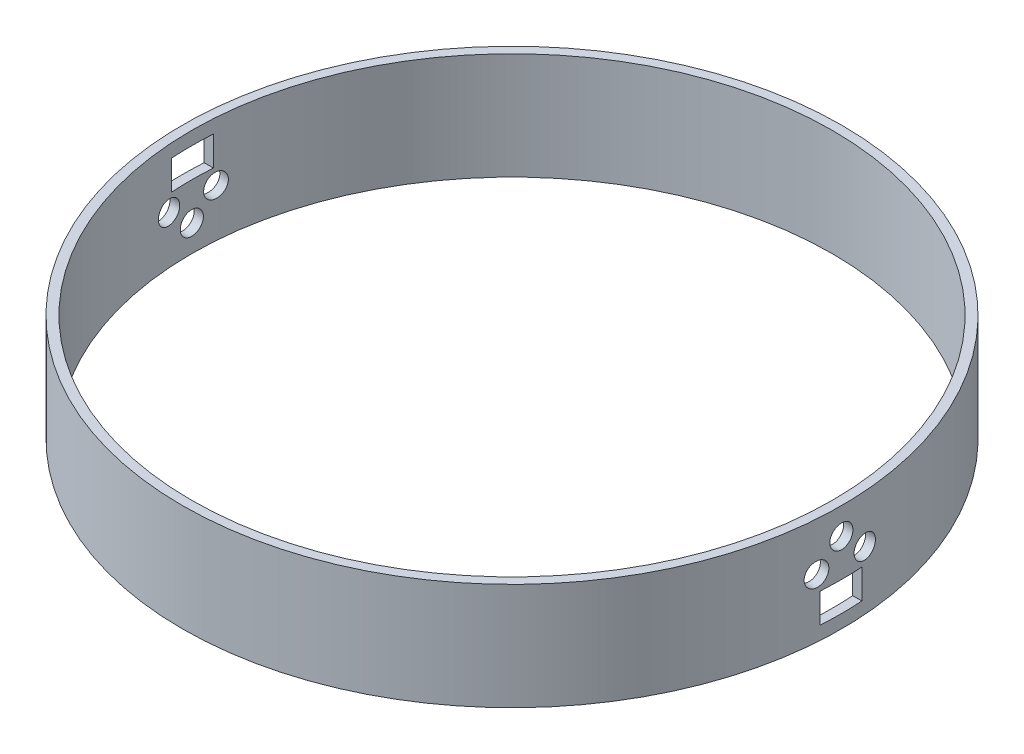
SolidWorks part; units mm, degrees
material "A-Glass Fiber"
ref_plane "Front Plane" through (0, 0, 0) normal (0, 0, 1) x (1, 0, 0)
ref_plane "Top Plane" through (0, 0, 0) normal (0, 1, 0) x (1, 0, 0)
ref_plane "Right Plane" through (0, 0, 0) normal (1, 0, 0) x (0, 0, -1)
sketch "Sketch1" plane through (0, 0, 0) normal (0, 1, 0) x (1, 0, 0)
  circle A0 centre (0, 0) radius 78.359
  circle A1 centre (0, 0) radius 76.1746
  dimension "D1" = 156.718
  dimension "D2" = 152.3492
extrude "Boss-Extrude1" add sketch "Sketch1" along normal blind 25.4
sketch "Sketch2" plane through (0, 0, 0) normal (1, 0, 0) x (0, 0, -1)
  line L0 (-78.359, 0) -> (78.359, 0) construction
  line L1 (-5, 3.175) -> (5, 3.175)
  line L2 (-5, 3.175) -> (-5, 10.175)
  line L3 (-5, 10.175) -> (5, 10.175)
  line L4 (5, 3.175) -> (5, 10.175)
  line L5 (-5, 3.175) -> (5, 10.175) construction
  line L6 (-5, 10.175) -> (5, 3.175) construction
  circle A0 centre (0, 19.065) radius 2.75
  point P0 (0, 6.675)
  dimension "D4" = 5.5
  dimension "D1" = 10
  dimension "D2" = 7
  dimension "D3" = 3.175
  dimension "D5" = 8.89
extrude "Cut-Extrude1" cut sketch "Sketch2" along normal through all
ref_plane "Plane1" through (0, 0, 0) normal (0.9973, 0, 0.0728) x (0, -1, 0)
sketch "Sketch5" plane through (0, 0, 0) normal (0.9973, 0, 0.0728) x (0, -1, 0)
  line L0 (-10.175, 0.7076) -> (-10.175, 10.681) construction
  circle A0 centre (-13.985, 0) radius 2.75
  dimension "D1" = 5.5
  dimension "D2" = 3.81
extrude "Cut-Extrude2" cut sketch "Sketch5" along normal through all
pattern_circular "CirPattern1" count 2 every 8.407 about axis through (0, 25.4, 0) along (0, 1, 0) of "Cut-Extrude2"
sketch "Sketch8" plane through (0, 0, 0) normal (1, 0, 0) x (0, 0, -1)
  line L0 (0, 25.4) -> (0, 0) construction
  line L1 (5, 15.225) -> (-5, 15.225)
  line L2 (5, 15.225) -> (5, 22.225)
  line L3 (5, 22.225) -> (-5, 22.225)
  line L4 (-5, 15.225) -> (-5, 22.225)
  line L5 (5, 15.225) -> (-5, 22.225) construction
  line L6 (5, 22.225) -> (-5, 15.225) construction
  line L8 (78.359, 25.4) -> (-78.359, 25.4) construction
  circle A0 centre (0, 6.335) radius 2.75
  point P0 (0, 18.725)
  dimension "D4" = 5.5
  dimension "D3" = 3.175
  dimension "D5" = 8.89
  dimension "D1" = 10
  dimension "D2" = 7
extrude "Cut-Extrude3" cut sketch "Sketch8" against normal through all
sketch "Sketch9" plane through (0, 0, 0) normal (0.9973, 0, 0.0728) x (0, -1, 0)
  line L0 (-15.225, -0.7076) -> (-15.225, -10.681) construction
  line L1 (-25.4, 0) -> (0, 0) construction
  circle A0 centre (-11.415, 0) radius 2.75
  dimension "D1" = 5.5
  dimension "D2" = 3.81
extrude "Cut-Extrude4" cut sketch "Sketch9" against normal through all
pattern_circular "CirPattern2" count 2 every 8.41 about axis through (0, 25.4, 0) along (0, 1, 0) of "Cut-Extrude4"
equation "\"Mid_Tube_Length\" = 1in"
equation "\"Bodytube_OD\" = 6.17in"
equation "\"Bodytube_ID\" = 5.998in"
equation "\"D1@Sketch1\"=\"Bodytube_OD\""
equation "\"D2@Sketch1\"= \"Bodytube_ID\""
equation "\"Camera_Cutout_Width\"=10mm"
equation "\"Camera_Cutout_Height\"=7mm"
equation "\"Fwd_Tube_Length\" = 40in"
equation "\"BKHD_Screw_Diam\"= 3.5mm"
equation "\"Fwd_BKHD_From_Top\" = 18in"
equation "\"Shear_Screw_Diameter\" = 0.086in"
equation "\"Shear_Screw_Coupler_Location\" = 4.5in"
equation "\"Motor_OD\" = 4in"
equation "\"Mid_Coupler_Length\" = 13in"
equation "\"Aft_Section_Length\"= 39in"
equation "\"AB_Coupler_OD_Length\"= 1in"
equation "\"AB_Coupling_Section_Length\"= 0.375in"
equation "\"AB_Coupler_Length\"= \"AB_Coupler_OD_Length\" + \"AB_Coupling_Section_Length\" * 2"
equation "\"Cutout_Angle\" = 80"
equation "\"AB_Paddle_Height\" = 0.375in"
equation "\"AB_Coupler_Num_Screws\"= 4"
equation "\"AB_BKHD_Thickness\" = 0.375in"
equation "\"AB_Mount_From_Bottom\" = 23.175in"
equation "\"Num_Cutouts\" = 3"
equation "\"AB_Coupler_OD\"= 6.17in"
equation "\"AB_Coupler_ID\"= 5.75in"
equation "\"AB_Coupler_Surface_Diameter\"= 5.998in"
equation "\"AB_Coupling_Screw_Diameter\"= 0.15748in"
equation "\"AB_Central_Bushing_Length\" = .4724in"
equation "\"Lead_Screw_Dist\" = 3.4in"
equation "\"Lead_Screw_Diam\" = 0.386in"
equation "\"Lead_Screw_Length\" = (\"Mid_Coupler_Length\" + 2*0.375in + 2*0.5in)"
equation "\"Paddle_Pin_Offset\" = .25in"
equation "\"Paddle_Pin_Radius\" = 2.25in"
equation "\"SS_Paddle_Pin_Radius\" = 2.25*0.66in"
equation "\"Paddle_Gear_OD\" = 3.2in"
equation "\"Drive_Gear_OD\" = 1.7in"
equation "\"Fin_Thickness\"= .118in"
equation "\"Guiderail_Cutout_Diameter\"= 1.5in"
equation "\"DB9_Hole_Dist\" = 25mm"
equation "\"DB9_Relief_Width\" = 0.47in"
equation "\"DB9_Relief_Hole_Offset\" = 0.09in"
equation "\"Airbrakes_Wire_Hole_Dia\" = .25in"
equation "\"Airbrakes_Wire_Hole_Dist\" = 1.1in"
equation "\"Servo_Gear_Offset\" = 0.5in"
equation "\"FWD_Shear_Screw_Dist\" = 1.5in"
equation "\"D2@Sketch2\"=\"Camera_Cutout_Height\""
equation "\"D1@Sketch2\"=\"Camera_Cutout_Width\""
equation "\"Camera_Screw_Dia\" = 0.216535"
equation "\"D4@Sketch2\"=\"Camera_Screw_Dia\""
equation "\"D1@Sketch5\"=\"Camera_Screw_Dia\""
equation "\"Camera_Hole_Angle\" = atn ( 2 / 3 * tan ( 12.5deg ) )"
equation "\"D2@CirPattern1\"=\"Camera_Hole_Angle\""
equation "\"D4@Sketch8\"=\"Camera_Screw_Dia\""
equation "\"D1@Sketch9\"=\"Camera_Screw_Dia\""
